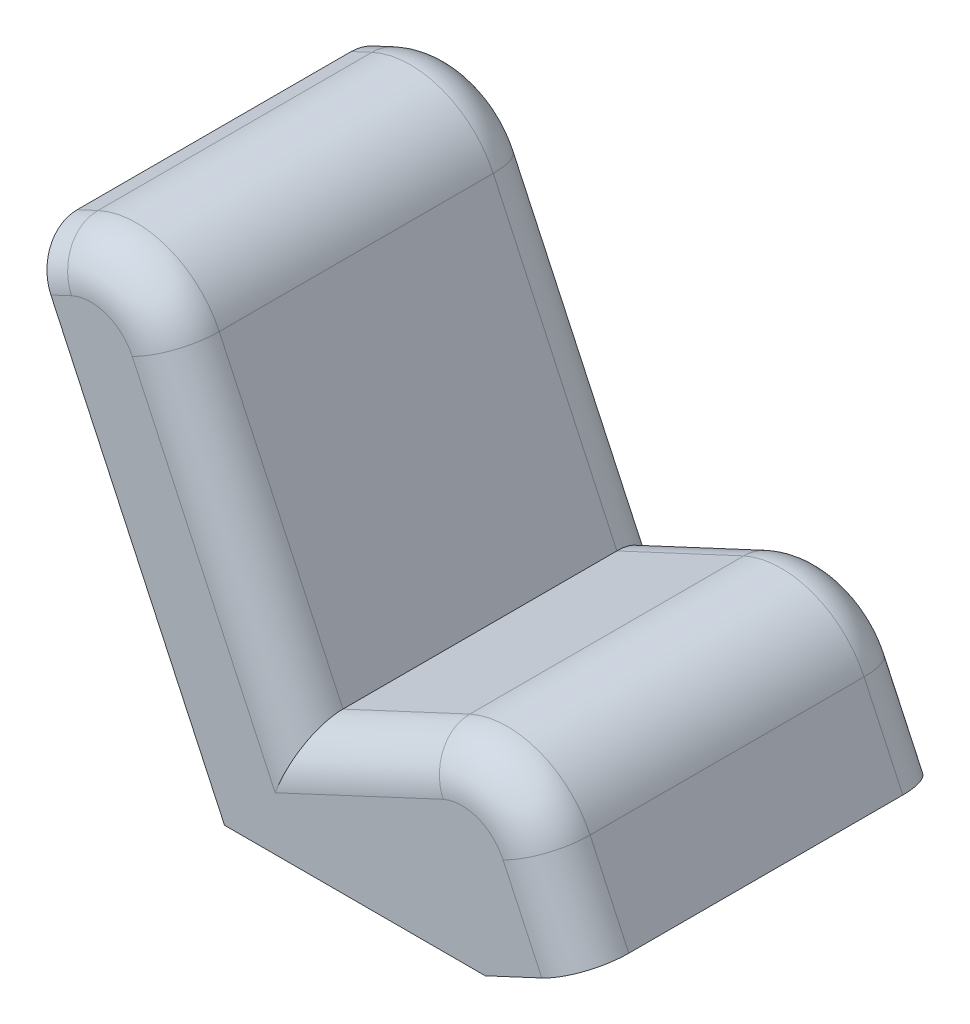
SolidWorks part; units mm, degrees
ref_plane "Front Plane" through (0, 0, 0) normal (0, 0, 1) x (1, 0, 0)
ref_plane "Top Plane" through (0, 0, 0) normal (0, 1, 0) x (1, 0, 0)
ref_plane "Right Plane" through (0, 0, 0) normal (1, 0, 0) x (0, 0, -1)
sketch "Sketch1" plane through (0, 0, 0) normal (0, 0, 1) x (1, 0, 0)
  line L0 (-42.2618, 90.6308) -> (0, 0)
  line L1 (0, 0) -> (57.1, 0)
  line L2 (57.1, 0) -> (78.5451, 10)
  line L3 (78.5451, 10) -> (70.0673, 28.1806)
  line L4 (43.7336, 37.9665) -> (15.9268, 25)
  line L5 (15.9268, 25) -> (-11.1518, 83.0701)
  line L6 (-37.7303, 92.7439) -> (-42.2618, 90.6308)
  arc A0 (70.0673, 28.1806) -> (43.7336, 37.9665) centre (51.9412, 19.7282) ccw
  arc A1 (-11.1518, 83.0701) -> (-37.7303, 92.7439) centre (-29.2779, 74.6177) ccw
  point P14 (-19.6041, 101.1962)
  dimension "D3" = 20
  dimension "D8" = 20
  dimension "D1" = 100
  dimension "D2" = 25
  dimension "D4" = 57.1
  dimension "D5" = 10
  dimension "D6" = 25
  dimension "D7" = 25
other "AlignGroup1"
other "AlignGroup2"
extrude "Boss-Extrude1" add sketch "Sketch1" along normal mid plane 80
sketch "Sketch2" plane through (0, 0, 0) normal (0, -1, 0) x (1, 0, 0)
  circle A0 centre (30, 0) radius 7.5
  dimension "D1" = 15
  dimension "D2" = 30
extrude "Boss-Extrude2" add sketch "Sketch2" along normal mid plane 10
fillet "Fillet1" radius 10 12 edges at (58.9079, 38.4756, -40) (-39.9961, 91.6873, -40) (-22.4375, 93.4116, -40) (58.9079, 38.4756, 40) (-39.9961, 91.6873, 40) (-22.4375, 93.4116, 40) (74.3062, 19.0903, -40) (29.8302, 31.4833, -40) (2.3875, 54.035, -40) (74.3062, 19.0903, 40) (29.8302, 31.4833, 40) (2.3875, 54.035, 40)
